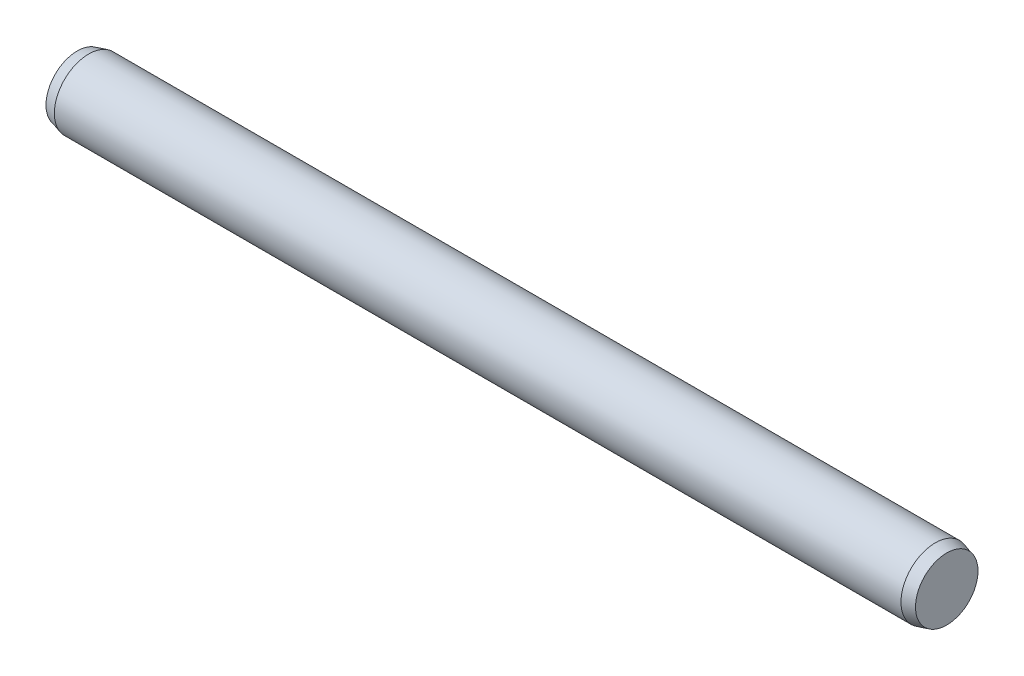
SolidWorks part; units mm, degrees
ref_plane "Front Plane" through (0, 0, 0) normal (0, 0, 1) x (1, 0, 0)
ref_plane "Top Plane" through (0, 0, 0) normal (0, 1, 0) x (1, 0, 0)
ref_plane "Right Plane" through (0, 0, 0) normal (1, 0, 0) x (0, 0, -1)
sketch "Sketch1" plane through (0, 0, 0) normal (0, 0, 1) x (1, 0, 0)
  line L0 (-18.5, 0) -> (18.5, 0) construction
  line L1 (18.5, 1.5) -> (18.5, -1.5) construction
  line L2 (-18.5, 1.5) -> (-18.5, -1.5) construction
  line L3 (19, 1.5) -> (19, -1.5) construction
  line L4 (-19, 1.5) -> (-19, -1.5) construction
  line L5 (-18.5, 0) -> (-19, 0) construction
  line L6 (18.5, 0) -> (19, 0) construction
  dimension "Dia" = 3
  dimension "C" = 0.5
  dimension "D1" = 0.5
  dimension "Length" = 38
sketch "Sketch2" plane through (0, 0, 0) normal (1, 0, 0) x (0, 0, -1)
  circle A0 centre (0, 0) radius 1.5
extrude "Extrude1" add sketch "Sketch2" against normal up to vertex (18.5 mm away) and the other way up to vertex (18.5 mm away) up to point (-18.5, 1.5, 0) other way up to point (18.5, 1.5, 0)
sketch "Sketch3" plane through (18.5, 0, 0) normal (1, 0, 0) x (0, 0, -1)
  circle A1 centre (0, 0) radius 1.5
  circle A2 centre (0, 0) radius 1.5
  dimension "D1" = 0
extrude "Extrude2" add sketch "Sketch3" along normal up to vertex (0.5 mm away) draft 15 up to point (19, 0, 0)
sketch "Sketch4" plane through (-18.5, 0, 0) normal (-1, 0, 0) x (0, 0, 1)
  circle A1 centre (0, 0) radius 1.5
  circle A2 centre (0, 0) radius 1.5
  dimension "D1" = 0
extrude "Extrude3" add sketch "Sketch4" along normal up to vertex (0.5 mm away) draft 15 up to point (-19, 0, 0)
sketch "Sketch5" plane through (0, 0, 0) normal (0, 1, 0) x (1, 0, 0)
  line L0 (-20.2941, 0) -> (21.5533, 0) construction
equation "\"D1@Sketch1\" = \"C@Sketch1\""
